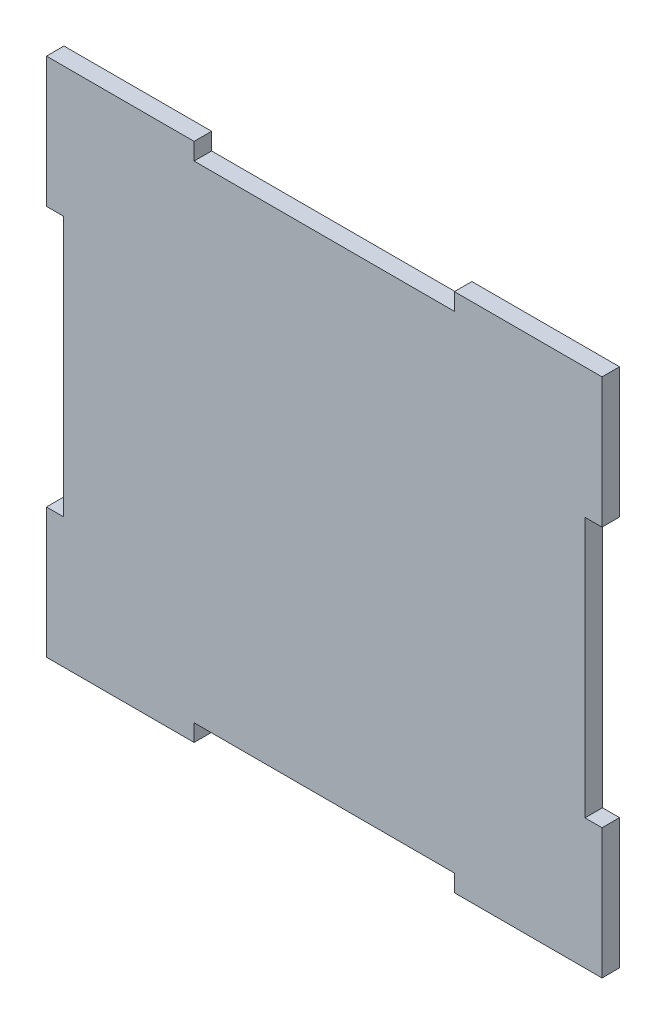
SolidWorks part; units mm, degrees
ref_plane "Front Plane" through (0, 0, 0) normal (0, 0, 1) x (1, 0, 0)
ref_plane "Top Plane" through (0, 0, 0) normal (0, 1, 0) x (1, 0, 0)
ref_plane "Right Plane" through (0, 0, 0) normal (1, 0, 0) x (0, 0, -1)
sketch "Sketch1" plane through (0, 0, 0) normal (0, 0, 1) x (1, 0, 0)
  line L1 (-53.36, 50) -> (53.36, 50)
  line L2 (-53.36, 50) -> (-53.36, -50)
  line L3 (-53.36, -50) -> (53.36, -50)
  line L4 (53.36, 50) -> (53.36, -50)
  line L5 (-53.36, 50) -> (53.36, -50) construction
  line L6 (-53.36, -50) -> (53.36, 50) construction
  point P0 (0, 0)
  dimension "D1" = 100
  dimension "D2" = 106.72
extrude "Boss-Extrude1" add sketch "Sketch1" along normal blind 3.36
sketch "Sketch2" [suppressed] plane through (0, 0, 3.36) normal (0, 0, 1) x (1, 0, 0)
  line L0 (50, 50) -> (-50, 50) construction
  line L1 (-25, 50) -> (25, 50)
  line L2 (-25, 50) -> (-25, 53.36)
  line L3 (-25, 53.36) -> (25, 53.36)
  line L4 (25, 50) -> (25, 53.36)
  line L5 (0, 0) -> (0, 53.36) construction
  line L6 (0, 0) -> (50, 0) construction
  line L7 (50, -50) -> (50, 50) construction
  dimension "D1" = 3.36
  dimension "D2" = 50
sketch "Sketch8" plane through (0, 0, 0) normal (0, 0, -1) x (-1, 0, 0)
  line L0 (0, 0) -> (0, 50) construction
  line L1 (-53.36, 50) -> (53.36, 50) construction
  line L2 (0, 0) -> (53.36, 0) construction
  line L3 (53.36, 50) -> (53.36, -50) construction
  line L5 (-25, 50) -> (25, 50)
  line L6 (-25, 50) -> (-25, 53.44)
  line L7 (-25, 53.44) -> (25, 53.44)
  line L8 (25, 50) -> (25, 53.44)
  dimension "D1" = 50
  dimension "D2" = 3.44
extrude "Boss-Extrude4" [suppressed] add sketch "Sketch8" against normal blind 3.36
mirror "Mirror4" [suppressed] about plane through (0, 0, 0) normal (0, 1, 0)
sketch "Sketch9" plane through (0, 0, 0) normal (0, 0, -1) x (-1, 0, 0)
  line L0 (0, 0) -> (53.36, 0) construction
  line L1 (53.36, 50) -> (53.36, -50) construction
  line L3 (53.36, 25) -> (56.8, 25)
  line L4 (53.36, 25) -> (53.36, -25)
  line L5 (53.36, -25) -> (56.8, -25)
  line L6 (56.8, 25) -> (56.8, -25)
  dimension "D1" = 50
  dimension "D2" = 3.44
extrude "Boss-Extrude5" [suppressed] add sketch "Sketch9" against normal blind 3.36
mirror "Mirror5" [suppressed] about plane through (0, 0, 0) normal (1, 0, 0)
sketch "Sketch10" plane through (0, 0, 3.36) normal (0, 0, 1) x (1, 0, 0)
  line L0 (0, 0) -> (0, 50) construction
  line L1 (53.36, 50) -> (-53.36, 50) construction
  line L3 (-25, 50) -> (25, 50)
  line L4 (-25, 50) -> (-25, 46.72)
  line L5 (-25, 46.72) -> (25, 46.72)
  line L6 (25, 50) -> (25, 46.72)
  dimension "D2" = 50
  dimension "D1" = 3.28
extrude "Cut-Extrude1" cut sketch "Sketch10" against normal blind 3.36
mirror "Mirror6" about plane through (0, 0, 0) normal (0, 1, 0) of "Cut-Extrude1"
sketch "Sketch11" plane through (0, 0, 3.36) normal (0, 0, 1) x (1, 0, 0)
  line L0 (0, 0) -> (53.36, 0) construction
  line L1 (53.36, -50) -> (53.36, 50) construction
  line L3 (53.36, 25) -> (50.08, 25)
  line L4 (53.36, 25) -> (53.36, -25)
  line L5 (53.36, -25) -> (50.08, -25)
  line L6 (50.08, 25) -> (50.08, -25)
  dimension "D2" = 50
  dimension "D1" = 3.28
extrude "Cut-Extrude2" cut sketch "Sketch11" against normal through all
mirror "Mirror7" about plane through (0, 0, 0) normal (1, 0, 0) of "Cut-Extrude2"
sketch "Sketch12" plane through (0, 0, 3.36) normal (0, 0, 1) x (1, 0, 0)
  line L0 (-53.36, -25) -> (-53.36, -50) construction
  line L1 (-53.36, -50) -> (-25, -50) construction
  line L2 (-34.3045, -26.1405) -> (-34.3045, 22.133) construction
  line L3 (-3.1998, 6.8595) -> (-3.1998, -21.0405) construction
  circle A0 centre (-34.3045, -26.1405) radius 1600
  circle A1 centre (-31.0001, 22.133) radius 3.3045
  circle A2 centre (-3.1998, -21.0405) radius 1.6
  circle A3 centre (-3.1998, 6.8595) radius 1.6
  dimension "D1" = 3200
  dimension "D2" = 19.0555
  dimension "D3" = 23.8595
  dimension "D4" = 6.6089
  dimension "D5" = 48.2735
  dimension "D6" = 3.2
  dimension "D7" = 5.1
  dimension "D8" = 3.2
  dimension "D9" = 27.8002
  dimension "D10" = 27.9
extrude "Cut-Extrude3" [suppressed] cut sketch "Sketch12" against normal blind 10
sketch "Sketch13" plane through (0, 0, 3.36) normal (0, 0, 1) x (1, 0, 0)
  line L0 (29.3057, -17.2496) -> (7.7192, -17.2496) construction
  line L1 (53.36, -50) -> (53.36, -25) construction
  line L2 (25, -50) -> (53.36, -50) construction
  circle A0 centre (29.3057, -17.2496) radius 2
  circle A1 centre (-12.9751, 3.9716) radius 2
  circle A2 centre (-12.9751, -38.4708) radius 2
  dimension "D1" = 4
  dimension "D2" = 42.4424
  dimension "D3" = 42.2808
  dimension "D4" = 24.0543
  dimension "D5" = 32.7504
extrude "Cut-Extrude4" [suppressed] cut sketch "Sketch13" against normal blind 10
sketch "Sketch18" plane through (0, 0, 0) normal (0, 0, -1) x (-1, 0, 0)
  line L0 (-37.4, -4.7) -> (-37.4, 6.3)
  line L1 (-37.4, 6.3) -> (-46.9, 6.3)
  line L2 (-46.9, 6.3) -> (-46.9, -4.7)
  line L3 (-46.9, -4.7) -> (-37.4, -4.7)
  line L24 (-50.08, 25) -> (-50.08, -25) construction
  line L25 (-53.36, 50) -> (-25, 50) construction
  point P0 (-37.4, -4.7)
  dimension "D1" = 3.18
  dimension "D2" = 9.5
  dimension "D3" = 11
  dimension "D4" = 43.7
extrude "Cut-Extrude5" [suppressed] cut sketch "Sketch18" against normal blind 10
equation "\"Sheet Thickness\"= 3.36mm"
equation "\"Height\"= 100mm"
equation "\"Length\"= 200mm"
equation "\"Width\"= 100mm"
equation "\"D1@Boss-Extrude1\"=\"Sheet Thickness\""
equation "\"D1@Sketch2\"=\"Sheet Thickness\""
equation "\"D2@Sketch2\"=\"Height\"/2"
equation "\"Kerf\"= .08mm"
equation "\"D2@Sketch9\"=\"Sheet Thickness\"+\"Kerf\""
equation "\"D1@Sketch9\"      = \"Height\"/2"
equation "\"D2@Sketch8\"=\"Sheet Thickness\"+\"Kerf\""
equation "\"D1@Sketch10\"=\"Sheet Thickness\"-\"Kerf\""
equation "\"D1@Sketch11\"=\"Sheet Thickness\"-\"Kerf\""
equation "\"D2@Sketch11\"=\"Height\"/2"
equation "\"D2@Sketch1\"  = \"Width\" +(\"Sheet Thickness\"*2)"
equation "\"D1@Sketch1\"   = \"Width\""
